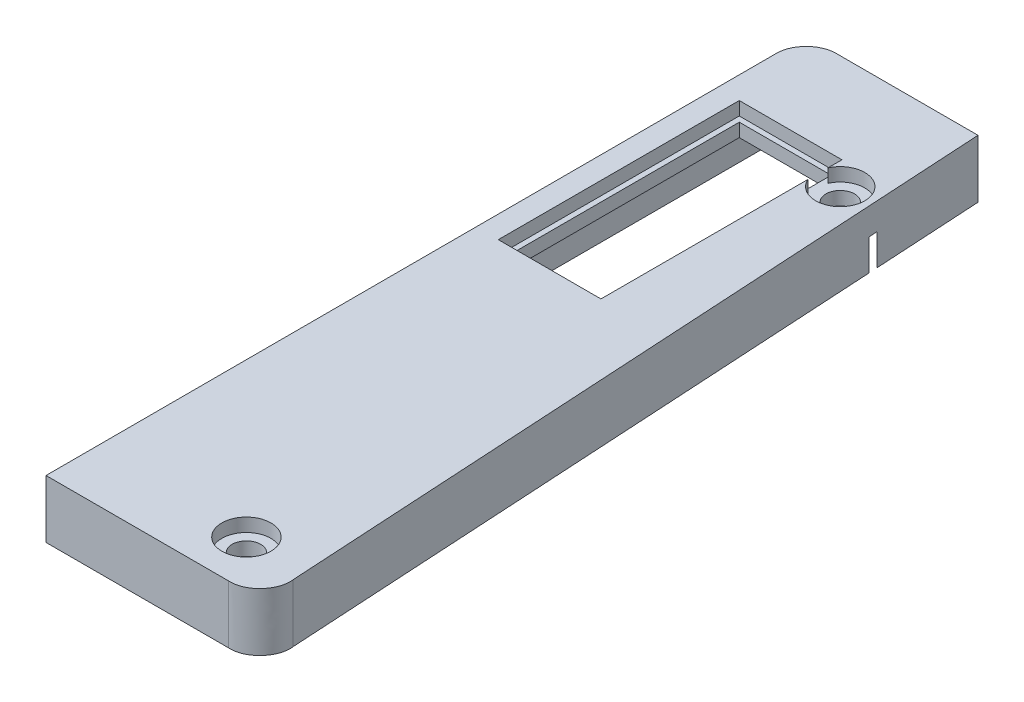
SolidWorks part; units mm, degrees
ref_plane "前视基准面" through (0, 0, 0) normal (0, 0, 1) x (1, 0, 0)
ref_plane "上视基准面" through (0, 0, 0) normal (0, 1, 0) x (1, 0, 0)
ref_plane "右视基准面" through (0, 0, 0) normal (1, 0, 0) x (0, 0, -1)
other "Configuration Table"
sketch "草图1" plane through (0, 0, 0) normal (0, 1, 0) x (1, 0, 0)
  spline S0 degree 3 poles (79.8, -135) (79.7853, -107.6953) (79.7707, -80.3907) (79.756, -53.086) knots 0 0 0 0 1 1 1 1
  spline S1 degree 3 poles (100.25, -135) (93.4333, -135) (86.6167, -135) (79.8, -135) knots 0 0 0 0 1 1 1 1
  spline S2 degree 3 poles (103.75, -131.25) (104.0238, -133.1898) (102.2041, -135.1396) (100.25, -135) knots 0 0 0 0 1 1 1 1
  spline S3 degree 3 poles (99, -49.784) (100.5833, -76.9393) (102.1667, -104.0947) (103.75, -131.25) knots 0 0 0 0 1 1 1 1
  spline S4 degree 3 poles (83.058, -49.784) (88.372, -49.784) (93.686, -49.784) (99, -49.784) knots 0 0 0 0 1 1 1 1
  spline S5 degree 3 poles (79.756, -53.086) (79.756, -51.3571) (81.3291, -49.784) (83.058, -49.784) knots 0 0 0 0 1 1 1 1
sketch "草图2" plane through (0, 0, 0) normal (0, 1, 0) x (1, 0, 0)
  line L0 (99, -49.784) -> (103.75, -131.25) construction
  line L1 (97.1132, -51.784) -> (101.7582, -131.4483) construction
  line L2 (97.1132, -51.784) -> (97.5472, -59.2269)
  line L3 (99, -49.784) -> (99.7015, -61.8151)
  line L4 (97.917, -65.5701) -> (101.7582, -131.4483)
  line L5 (99.7559, -62.7491) -> (103.75, -131.25)
  line L6 (100.25, -135) -> (79.8, -135) construction
  line L7 (100.3213, -133) -> (81.7989, -133) construction
  line L8 (81.7989, -133) -> (95.701, -133)
  line L9 (98.299, -133) -> (100.3213, -133)
  arc A1 (97.917, -65.5701) -> (99.7559, -62.7491) centre (96.266, -62.484) ccw
  arc A2 (99.7015, -61.8151) -> (97.5472, -59.2269) centre (96.266, -62.484) ccw
  arc A3 (95.701, -133) -> (98.299, -133) centre (97, -129.75) ccw
  spline S0 degree 3 poles (-3011.1303, -2632.3397) (2997.6326, 2688.3459) (-2513.3, -3216.226) (2380.8166, 3144.7422) knots -10.683629 -10.683629 -10.683629 -10.683629 11.683601 11.683601 11.683601 11.683601 only from (103.75, -131.25) to (100.25, -135) construction
  spline S1 degree 3 poles (4100.1545, -134.9997) (1426.7324, -135.0003) (-1246.6896, -134.9997) (-3920.1117, -135.0003) knots -195.59435 -195.59435 -195.59435 -195.59435 196.594702 196.594702 196.594702 196.594702 only from (100.25, -135) to (79.8, -135) construction
  spline S2 degree 3 poles (81.9486, -4134.9276) (80.5015, -1441.0026) (79.0545, 1252.9225) (77.6074, 3946.8475) knots -48.830818 -48.830818 -48.830818 -48.830818 49.83089 49.83089 49.83089 49.83089 only from (79.8, -135) to (79.756, -53.086) construction
  spline S3 degree 3 poles (3285.4637, 2329.7478) (-2910.7075, -2767.5236) (2797.528, 2940.7063) (-2299.8543, -3255.5872) knots -12.105497 -12.105497 -12.105497 -12.105497 13.105627 13.105627 13.105627 13.105627 only from (79.756, -53.086) to (83.058, -49.784) construction
  spline S4 degree 3 poles (-3916.9094, -49.7838) (-1244.9561, -49.7842) (1426.9972, -49.7838) (4098.9505, -49.7842) knots -250.907505 -250.907505 -250.907505 -250.907505 251.906442 251.906442 251.906442 251.906442 only from (83.058, -49.784) to (99, -49.784) construction
  spline S6 degree 3 poles (103.75, -131.25) (104.0238, -133.1898) (102.2041, -135.1396) (100.25, -135) knots 0 0 0 0 1 1 1 1
  spline S7 degree 3 poles (100.25, -135) (93.4333, -135) (86.6167, -135) (79.8, -135) knots 0 0 0 0 1 1 1 1
  spline S8 degree 3 poles (79.8, -135) (79.7853, -107.6953) (79.7707, -80.3907) (79.756, -53.086) knots 0 0 0 0 1 1 1 1
  spline S9 degree 3 poles (79.756, -53.086) (79.756, -51.3571) (81.3291, -49.784) (83.058, -49.784) knots 0 0 0 0 1 1 1 1
  spline S10 degree 3 poles (83.058, -49.784) (88.372, -49.784) (93.686, -49.784) (99, -49.784) knots 0 0 0 0 1 1 1 1
  spline S11 degree 3 poles (99, -49.784) (100.5833, -76.9393) (102.1667, -104.0947) (103.75, -131.25) knots 0 0 0 0 1 1 1 1 construction
  spline S12 degree 1 poles (81.756, -53.0856) (83.058, -51.784) knots 0 0 1 1 construction
  spline S13 degree 1 poles (83.058, -51.784) (97.1132, -51.784) knots 0 0 1 1 construction
  spline S15 degree 1 poles (101.7582, -131.4483) (100.3213, -133) knots 0 0 1 1 construction
  spline S17 degree 1 poles (81.7989, -133) (81.756, -53.0856) knots 0 0 1 1 construction
  spline S18 degree 3 poles (81.756, -53.0856) (81.7561, -52.9387) (81.8148, -52.6732) (82.1445, -52.172) (82.6457, -51.8426) (82.9111, -51.784) (83.058, -51.784) knots 0.000245 0.000245 0.000245 0.000245 0.250184 0.500123 0.750061 1 1 1 1
  spline S19 degree 3 poles (83.058, -51.784) (84.2293, -51.784) (86.5718, -51.784) (90.0856, -51.784) (93.5994, -51.784) (95.9419, -51.784) (97.1132, -51.784) knots 0 0 0 0 0.220412 0.440823 0.661235 0.881647 0.881647 0.881647 0.881647
  spline S21 degree 3 poles (101.7582, -131.4483) (101.7621, -131.4765) (101.7727, -131.5505) (101.773, -131.5578) (101.7797, -131.6373) (101.7743, -131.7568) (101.7135, -132.0675) (101.411, -132.5714) (100.9289, -132.91) (100.6236, -132.9934) (100.5029, -133.0075) (100.4252, -133.0067) (100.4143, -133.0067) (100.3472, -133.0018) (100.3213, -133) knots -0.013961 -0.013961 -0.013961 -0.013961 0.002072 0.018105 0.05017 0.114302 0.242564 0.499089 0.755613 0.883876 0.948007 0.980072 0.996105 1.012138 1.012138 1.012138 1.012138
  spline S23 degree 3 poles (81.7989, -133) (81.7953, -126.3405) (81.7882, -113.0214) (81.7775, -93.0428) (81.7667, -73.0642) (81.7596, -59.7452) (81.756, -53.0856) knots 0.024403 0.024403 0.024403 0.024403 0.2683 0.512197 0.756094 0.999992 0.999992 0.999992 0.999992
  dimension "D2" = 7
  dimension "D5" = 7
  dimension "D3" = 2.734
  dimension "D4" = 12.7
  dimension "D6" = 0.734
  dimension "D7" = 67.266
  dimension "D1" = 2
extrude "凸台-拉伸1" add sketch "草图2" along normal blind 3.5
sketch "草图3" plane through (0, 3.5, 0) normal (0, 1, 0) x (1, 0, 0)
  line L0 (81.756, -55.7878) -> (81.756, -122.4143) construction
  circle A0 centre (83.7, -120.9) radius 10
  dimension "D2" = 20
  dimension "D1" = 2
  dimension "D3" = 3.9
  dimension "D4" = 14.1
extrude "切除-拉伸1" cut sketch "草图3" against normal through all
sketch "草图4" plane through (0, 3.5, 0) normal (0, 1, 0) x (1, 0, 0)
  line L0 (103.75, -131.25) -> (99, -49.784)
  line L1 (79.8, -135) -> (100.25, -135)
  line L2 (79.756, -53.086) -> (79.8, -135)
  line L3 (99, -49.784) -> (83.058, -49.784)
  line L4 (103.75, -131.25) -> (99, -49.784)
  line L5 (79.8, -135) -> (100.25, -135)
  line L6 (79.756, -53.086) -> (79.8, -135)
  line L7 (99, -49.784) -> (83.058, -49.784)
  spline S32 degree 3 poles (2380.8347, 3144.7656) (-2513.3075, -3216.2327) (2997.6264, 2688.338) (-3011.1082, -2632.3201) knots -10.683629 -10.683629 -10.683629 -10.683629 11.683601 11.683601 11.683601 11.683601 only from (100.25, -135) to (103.75, -131.25)
  spline S33 degree 3 poles (-2299.7758, -3255.4917) (2797.4956, 2940.6795) (-2910.7343, -2767.556) (3285.5592, 2329.8263) knots -12.105497 -12.105497 -12.105497 -12.105497 13.105627 13.105627 13.105627 13.105627 only from (83.058, -49.784) to (79.756, -53.086)
  spline S34 degree 3 poles (100.25, -135) (102.2041, -135.1396) (104.0238, -133.1898) (103.75, -131.25) knots 0 0 0 0 1 1 1 1
  spline S35 degree 3 poles (83.058, -49.784) (81.3291, -49.784) (79.756, -51.3571) (79.756, -53.086) knots 0 0 0 0 1 1 1 1
  dimension "D1" = 0
extrude "凸台-拉伸2" add sketch "草图4" along normal blind 1.5
sketch "草图5" plane through (0, 0, 0) normal (0, -1, 0) x (1, 0, 0)
  line L0 (97.1132, 51.784) -> (83.058, 51.784) construction
  line L1 (84.85, 51.784) -> (94.35, 51.784)
  line L2 (84.85, 51.784) -> (84.85, 49.784)
  line L3 (84.85, 49.784) -> (94.35, 49.784)
  line L4 (94.35, 51.784) -> (94.35, 49.784)
  line L5 (89.6, 51.784) -> (89.6, 49.784) construction
  spline S0 degree 3 poles (83.058, 49.784) (88.372, 49.784) (93.686, 49.784) (99, 49.784) knots 0 0 0 0 1 1 1 1 construction
  dimension "D1" = 9.4
  dimension "D2" = 9.5
extrude "切除-拉伸2" cut sketch "草图5" against normal blind 3
sketch "草图6" plane through (0, 3.5, 0) normal (0, -1, 0) x (1, 0, 0)
  line L1 (82.256, 86.784) -> (93.756, 86.784)
  line L2 (82.256, 86.784) -> (82.256, 59.784)
  line L3 (82.256, 59.784) -> (93.756, 59.784)
  line L4 (93.756, 86.784) -> (93.756, 59.784)
  point P7 (0, 0)
  dimension "D1" = 2.5
  dimension "D2" = 10
  dimension "D3" = 27
  dimension "D4" = 11.5
extrude "切除-拉伸3" cut sketch "草图6" against normal blind 3 contours L1 L4 L3 L2
sketch "草图7" plane through (0, 3.5, 0) normal (0, -1, 0) x (1, 0, 0)
  circle A0 centre (96.266, 62.484) radius 1.6
  circle A1 centre (97, 129.75) radius 1.6
  arc A2 (98.299, 133) -> (95.701, 133) centre (97, 129.75) ccw construction
  arc A3 (99.7559, 62.7491) -> (97.917, 65.5701) centre (96.266, 62.484) ccw construction
  dimension "D1" = 3.2
extrude "切除-拉伸4" cut sketch "草图7" against normal blind 3
sketch "草图8" plane through (0, 5, 0) normal (0, 1, 0) x (1, 0, 0)
  line L8 (99, -49.784) -> (83.058, -49.784)
  line L9 (79.756, -53.086) -> (79.8, -135)
  line L10 (79.8, -135) -> (100.25, -135)
  line L11 (103.75, -131.25) -> (99, -49.784)
  line L12 (99, -49.784) -> (83.058, -49.784)
  line L13 (79.756, -53.086) -> (79.8, -135)
  line L14 (79.8, -135) -> (100.25, -135)
  line L15 (103.75, -131.25) -> (99, -49.784)
  line L22 (93.756, -61.3604) -> (93.756, -59.784)
  line L26 (82.256, -59.784) -> (82.256, -86.784)
  line L27 (82.256, -86.784) -> (93.756, -86.784)
  line L28 (93.756, -86.784) -> (93.756, -59.784)
  line L29 (93.756, -59.784) -> (82.256, -59.784)
  line L30 (82.256, -59.784) -> (82.256, -86.784)
  line L31 (82.256, -86.784) -> (93.756, -86.784)
  line L32 (93.756, -86.784) -> (93.756, -63.6076)
  line L33 (93.756, -59.784) -> (82.256, -59.784)
  arc A1 (93.756, -63.6076) -> (93.756, -61.3604) centre (96.266, -62.484) ccw
  circle A2 centre (97, -129.75) radius 2.75
  spline S4 degree 3 poles (-1668.0898, -2480.4198) (2112.4028, 2207.7895) (-2177.8336, -2082.4507) (2510.4499, 1698.1087) knots -10.956614 -10.956614 -10.956614 -10.956614 11.956709 11.956709 11.956709 11.956709 only from (83.058, -49.784) to (79.756, -53.086)
  spline S5 degree 3 poles (1774.6185, 2349.4954) (-1853.2012, -2460.3915) (2289.051, 1977.7343) (-2259.4846, -1972.7626) knots -9.664568 -9.664568 -9.664568 -9.664568 10.664534 10.664534 10.664534 10.664534 only from (100.25, -135) to (103.75, -131.25)
  spline S6 degree 3 poles (83.058, -49.784) (81.3291, -49.784) (79.756, -51.3571) (79.756, -53.086) knots 0 0 0 0 1 1 1 1
  spline S7 degree 3 poles (100.25, -135) (102.2041, -135.1396) (104.0238, -133.1898) (103.75, -131.25) knots 0 0 0 0 1 1 1 1
  dimension "D3" = 5.5
  dimension "D4" = 5.5
  dimension "D1" = 0
  dimension "D2" = 0
extrude "凸台-拉伸3" add sketch "草图8" along normal blind 1.5
sketch "草图9" plane through (0, 3.5, 0) normal (0, -1, 0) x (1, 0, 0)
  line L11 (81.556, 87.984) -> (94.456, 87.984)
  line L12 (81.556, 87.984) -> (81.556, 58.584)
  line L13 (81.556, 58.584) -> (94.456, 58.584)
  line L14 (94.456, 87.984) -> (94.456, 58.584)
  line L15 (82.256, 86.784) -> (93.756, 86.784) construction
  line L16 (82.256, 59.784) -> (93.756, 59.784) construction
  line L17 (93.756, 86.784) -> (93.756, 59.784) construction
  line L20 (82.256, 86.784) -> (82.256, 59.784) construction
  dimension "D1" = 1.2
  dimension "D2" = 1.2
  dimension "D3" = 0.7
  dimension "D4" = 0.7
sketch "草图10" plane through (0, 3.5, 0) normal (0, -1, 0) x (1, 0, 0)
  line L0 (86.2, 125.2301) -> (88.7, 129.5603)
  line L1 (86.2, 116.5699) -> (88.7, 112.2397)
  line L2 (83.7, 120.9) -> (93.7, 120.9) construction
  arc A0 (88.7, 129.5603) -> (88.7, 112.2397) centre (83.7, 120.9) ccw
  arc A1 (81.7977, 130.7174) -> (79.7974, 130.107) centre (83.7, 120.9) ccw construction
  arc A2 (86.2, 125.2301) -> (86.2, 116.5699) centre (83.7, 120.9) ccw
  dimension "D1" = 10
  dimension "D2" = 60
extrude "切除-拉伸6" cut sketch "草图10" against normal offset from surface (2 mm away) 5.5 up to face at (82.4858, 0, 66.3413)
sketch "草图13" plane through (0, 3.5, 0) normal (0, -1, 0) x (1, 0, 0)
  line L1 (86.8, 100) -> (99.3, 100)
  line L2 (86.8, 100) -> (86.8, 89.784)
  line L3 (86.8, 89.784) -> (99.3, 89.784)
  line L4 (99.3, 100) -> (99.3, 89.784)
  dimension "D1" = 35
  dimension "D2" = 40
  dimension "D3" = 19.5
  dimension "D4" = 12.5
extrude "切除-拉伸10" cut sketch "草图13" against normal offset from surface (1.5 mm away) 5 up to face at (92.5029, 0, 121.1812)
sketch "草图14" plane through (0, 3.5, 0) normal (0, -1, 0) x (1, 0, 0)
  line L14 (82.256, 86.784) -> (93.756, 86.784) construction
  line L15 (82.256, 86.784) -> (93.756, 86.784)
  line L16 (82.256, 59.784) -> (93.756, 59.784) construction
  line L17 (93.756, 86.784) -> (93.756, 59.784) construction
  line L18 (93.156, 60.384) -> (93.156, 86.184)
  line L19 (82.856, 60.384) -> (93.156, 60.384)
  line L20 (82.856, 86.184) -> (82.856, 60.384)
  line L21 (93.156, 86.184) -> (82.856, 86.184)
  line L22 (93.156, 60.384) -> (93.156, 86.184)
  line L23 (82.856, 60.384) -> (93.156, 60.384)
  line L24 (82.856, 86.184) -> (82.856, 60.384)
  line L25 (93.156, 86.184) -> (82.856, 86.184)
  line L26 (82.256, 59.784) -> (93.756, 59.784)
  line L27 (93.756, 86.784) -> (93.756, 59.784)
  line M11 (82.256, 59.784) -> (82.256, 86.784)
  line M12 (82.256, 86.784) -> (93.756, 86.784)
  line M13 (93.756, 86.784) -> (93.756, 59.784)
  line M14 (93.756, 59.784) -> (82.256, 59.784)
  dimension "D1" = 0.6
extrude "凸台-拉伸5" add sketch "草图14" against normal offset from surface (1.5 mm away) 1.5 contours L25 L22 L23 L24 M11 M14 M13 M12 region at (88.006, 3.5, 86.4905) up to face at (97, 6.5, 132.5)
sketch "草图15" plane through (0, 5, 0) normal (0, 1, 0) x (1, 0, 0)
  circle A0 centre (96.266, -62.484) radius 2.75
  arc A1 (93.756, -63.6076) -> (93.756, -61.3604) centre (96.266, -62.484) ccw construction
